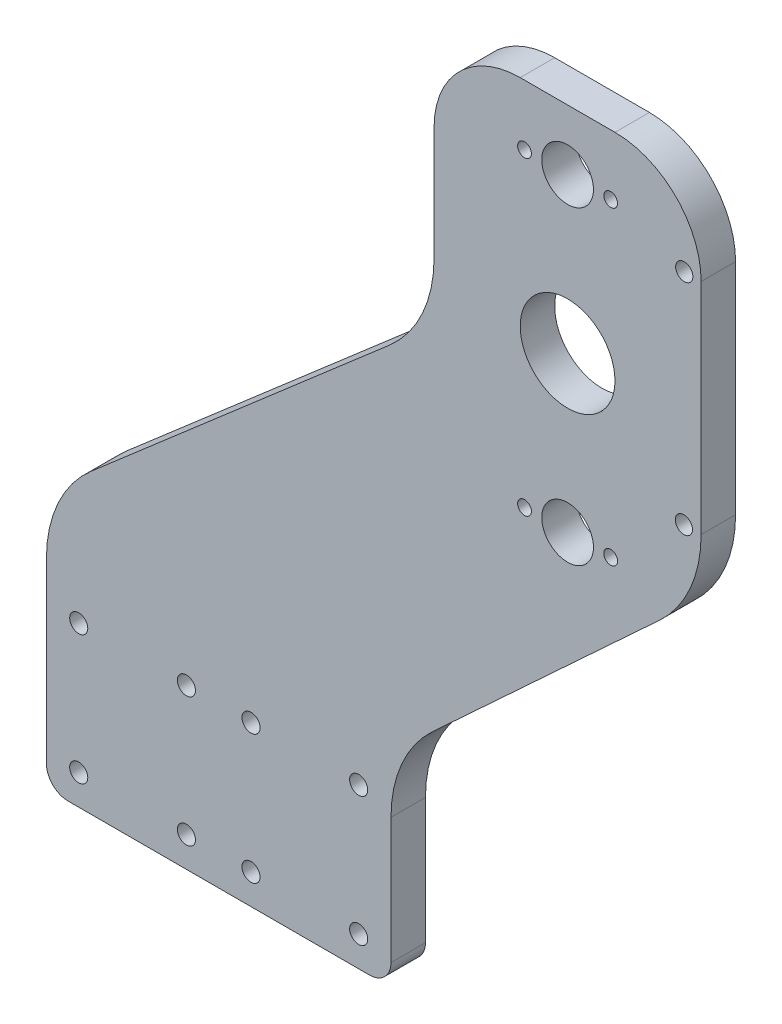
SolidWorks part; units mm, degrees
ref_plane "Front Plane" through (0, 0, 0) normal (0, 0, 1) x (1, 0, 0)
ref_plane "Top Plane" through (0, 0, 0) normal (0, 1, 0) x (1, 0, 0)
ref_plane "Right Plane" through (0, 0, 0) normal (1, 0, 0) x (0, 0, -1)
sketch "Sketch1" plane through (0, 0, 0) normal (0, 0, 1) x (1, 0, 0)
  line L0 (-23.7069, -89.4353) -> (-23.7069, -15.4242) construction
  line L1 (-58.7069, -89.4353) -> (11.2931, -89.4353)
  line L2 (-63.7069, -84.4353) -> (-63.7069, -43.1405)
  line L3 (-63.7069, -84.4353) -> (-23.7069, -84.4353) construction
  line L4 (16.2931, -84.4353) -> (16.2931, -55.2061)
  line L5 (46.2931, 108.5094) -> (68.2931, 108.5094)
  line L6 (26.2931, 88.5094) -> (26.2931, 62.2146)
  line L7 (57.2931, 108.5094) -> (57.2931, 22.5694) construction
  line L8 (88.2931, 88.5094) -> (88.2931, 37.6266)
  line L9 (-43.7069, -67.4353) -> (-43.7069, -84.4353) construction
  line L10 (-56.2069, -52.4353) -> (-31.2069, -52.4353) construction
  line L11 (15.933, 39.537) -> (-53.3469, -20.463)
  line L12 (78.6643, 15.6036) -> (25.9218, -33.1831)
  line L13 (-56.2069, -52.4353) -> (-56.2069, -82.4353) construction
  line L14 (-56.2069, -82.4353) -> (-31.2069, -82.4353) construction
  line L15 (-31.2069, -52.4353) -> (-31.2069, -82.4353) construction
  line L16 (-56.2069, -52.4353) -> (-31.2069, -82.4353) construction
  line L17 (-56.2069, -82.4353) -> (-31.2069, -52.4353) construction
  line L18 (57.2931, 94.5094) -> (57.2931, 22.5694) construction
  arc A0 (78.6643, 15.6036) -> (88.2931, 37.6266) centre (58.2931, 37.6266) ccw
  arc A1 (15.933, 39.537) -> (26.2931, 62.2146) centre (-3.7069, 62.2146) ccw
  arc A2 (16.2931, -55.2061) -> (25.9218, -33.1831) centre (46.2931, -55.2061) cw
  arc A3 (-63.7069, -43.1405) -> (-53.3469, -20.463) centre (-33.7069, -43.1405) cw
  arc A4 (88.2931, 88.5094) -> (68.2931, 108.5094) centre (68.2931, 88.5094) ccw
  arc A5 (46.2931, 108.5094) -> (26.2931, 88.5094) centre (46.2931, 88.5094) ccw
  arc A6 (16.2931, -84.4353) -> (11.2931, -89.4353) centre (11.2931, -84.4353) cw
  arc A7 (-58.7069, -89.4353) -> (-63.7069, -84.4353) centre (-58.7069, -84.4353) cw
  circle A8 centre (-56.2069, -52.4353) radius 2.1
  circle A9 centre (-31.2069, -52.4353) radius 2.1
  circle A10 centre (-31.2069, -82.4353) radius 2.1
  circle A11 centre (-56.2069, -82.4353) radius 2.1
  circle A12 centre (8.7931, -82.4353) radius 2.1
  circle A13 centre (-16.2069, -82.4353) radius 2.1
  circle A14 centre (-16.2069, -52.4353) radius 2.1
  circle A15 centre (8.7931, -52.4353) radius 2.1
  circle A16 centre (57.2931, 94.5094) radius 6
  circle A17 centre (57.2931, 22.5694) radius 6
  circle A18 centre (57.2931, 58.5394) radius 11
  circle A19 centre (84.2931, 37.6266) radius 2
  circle A20 centre (84.3759, 88.5283) radius 2
  circle A21 centre (47.2931, 94.5094) radius 1.6
  circle A22 centre (47.2931, 22.5694) radius 1.6
  circle A23 centre (67.2931, 94.5094) radius 1.6
  circle A24 centre (67.2931, 22.5694) radius 1.6
  point P0 (0, 0)
  point P1 (57.2931, 82.2289)
  point P15 (26.2931, 48.5094)
  point P20 (-63.7069, -29.4353)
  point P23 (88.2931, 108.5094)
  point P26 (26.2931, 108.5094)
  point P29 (16.2931, -89.4353)
  point P32 (-63.7069, -89.4353)
  point P35 (-43.7069, -67.4353)
  dimension "D5" = 30
  dimension "D6" = 20
  dimension "D7" = 5
  dimension "D14" = 71.94
  dimension "D12" = 4
  dimension "D16" = 10
  dimension "D17" = 10
  dimension "D1" = 80
  dimension "D2" = 22
  dimension "D3" = 90
  dimension "D4" = 60
  dimension "D8" = 25
  dimension "D9" = 60
  dimension "D10" = 22
  dimension "D11" = 60
  dimension "D13" = 30
  dimension "D15" = 14
extrude "Boss-Extrude1" add sketch "Sketch1" along normal blind 8
